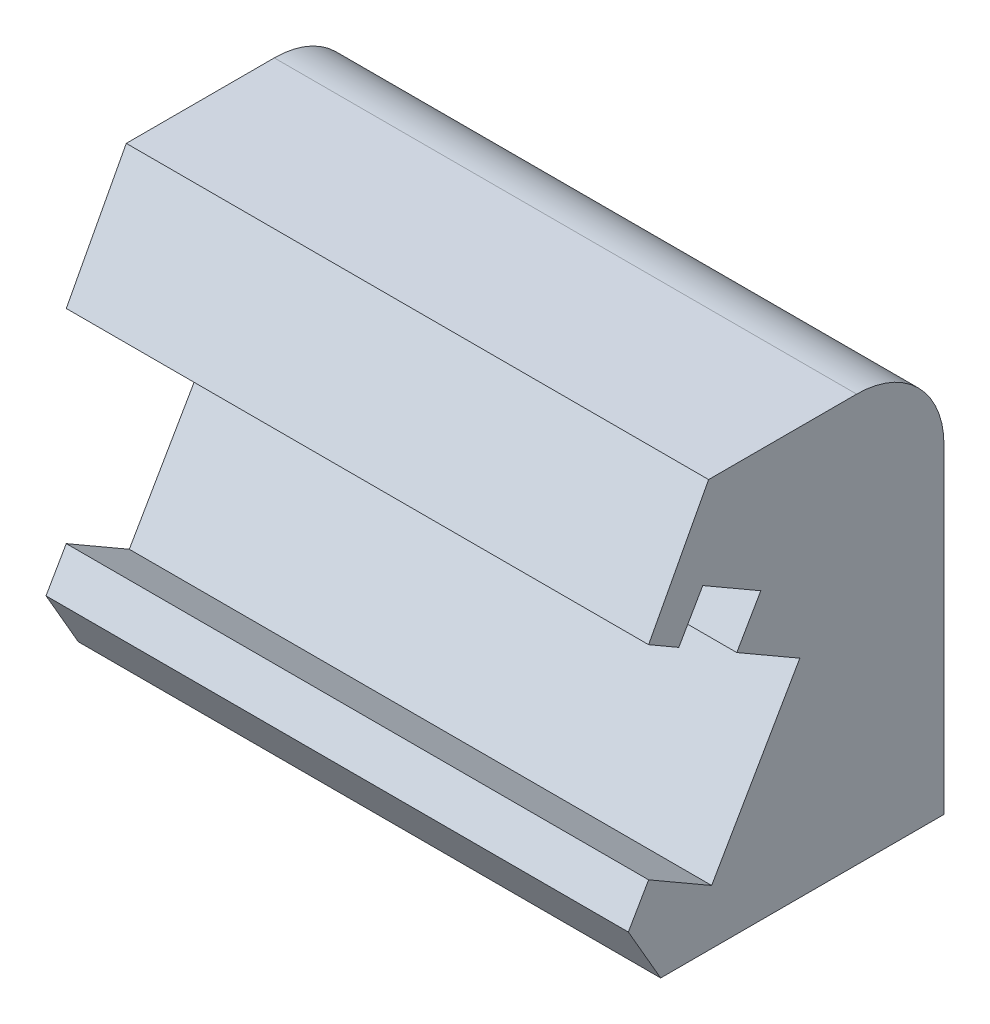
SolidWorks part; units mm, degrees
ref_plane "Front Plane" through (0, 0, 0) normal (0, 0, 1) x (1, 0, 0)
ref_plane "Top Plane" through (0, 0, 0) normal (0, 1, 0) x (1, 0, 0)
ref_plane "Right Plane" through (0, 0, 0) normal (1, 0, 0) x (0, 0, -1)
sketch "Sketch1" plane through (0, 0, 0) normal (0, 1, 0) x (1, 0, 0)
  line L0 (-58.88, 42.74) -> (-63.88, 37.74) construction
  line L1 (-63.88, 42.74) -> (63.88, 42.74) construction
  line L2 (-63.88, 42.74) -> (-63.88, -42.74) construction
  line L3 (-63.88, -42.74) -> (63.88, -42.74) construction
  line L4 (63.88, 42.74) -> (63.88, -42.74) construction
  line L5 (0, -42.74) -> (0, 42.74) construction
  line L6 (-63.88, 0) -> (16.3689, 0) construction
  line L8 (-50, 35) -> (50, 35)
  line L9 (-50, 35) -> (-50, -35)
  line L10 (-50, -35) -> (50, -35)
  line L11 (50, 35) -> (50, -35)
  line L12 (0, -35) -> (0, 35) construction
  line L72 (-44.4004, 35) -> (-50, 28.9178)
  line L85 (34.8689, 0) -> (63.88, 0) construction
  line L87 (34.8689, 0) -> (50, 0) construction
  dimension "D1" = 85.48
  dimension "D2" = 127.76
  dimension "D3" = 5
  dimension "D4" = 5
  dimension "D5" = 100
  dimension "D6" = 70
sketch "Sketch13" plane through (-31.8, 0, 0) normal (1, 0, 0) x (0, 0, -1)
  line L0 (-3.5499, 4.5487) -> (-3.5499, 16.1374) construction
  line L1 (6.7465, 9.38) -> (3.7315, 14.6021)
  line L2 (3.7315, 14.6021) -> (8.3929, 23.3814)
  line L6 (16.4766, 9.38) -> (6.7465, 9.38)
  line L7 (-35, 9.38) -> (35, 9.38) construction
  line L8 (8.3929, 23.3814) -> (13.4766, 23.3814)
  line L9 (16.4766, 20.3814) -> (16.4766, 9.38)
  arc A0 (13.4766, 23.3814) -> (16.4766, 20.3814) centre (13.4766, 20.3814) cw
  dimension "D3" = 3
  dimension "D1" = 9.94
  dimension "D4" = 9.7301
  dimension "D5" = 5.2221
  dimension "D6" = 120
extrude "Boss-Extrude1" add sketch "Sketch13" along normal blind 10 and the other way blind 10 separate body
sketch "Sketch15" plane through (-31.8, 0, 0) normal (1, 0, 0) x (0, 0, -1)
  line L0 (10.1844, 19.1789) -> (9.3607, 17.7521)
  line L1 (6.3324, 12.5069) -> (5.6368, 11.3021)
  line L2 (9.3607, 17.7521) -> (11.5257, 16.5021)
  line L3 (11.5257, 16.5021) -> (8.4974, 11.2569)
  line L4 (8.4974, 11.2569) -> (6.3324, 12.5069)
  line L5 (6.3324, 19.5005) -> (7.3688, 18.9021)
  line L6 (7.3688, 18.9021) -> (8.1925, 20.3289)
  line L7 (3.4993, 17.3612) -> (10.4258, 13.3622) construction
  line L8 (3.6179, 14.7989) -> (6.3324, 19.5005)
  line L9 (8.1925, 20.3289) -> (10.1844, 19.1789)
  line L10 (5.6368, 11.3021) -> (3.6179, 14.7989)
  line L11 (8.3929, 23.3814) -> (3.7315, 14.6021) construction
extrude "Cut-Extrude1" cut sketch "Sketch15" against normal blind 10 and the other way blind 10
